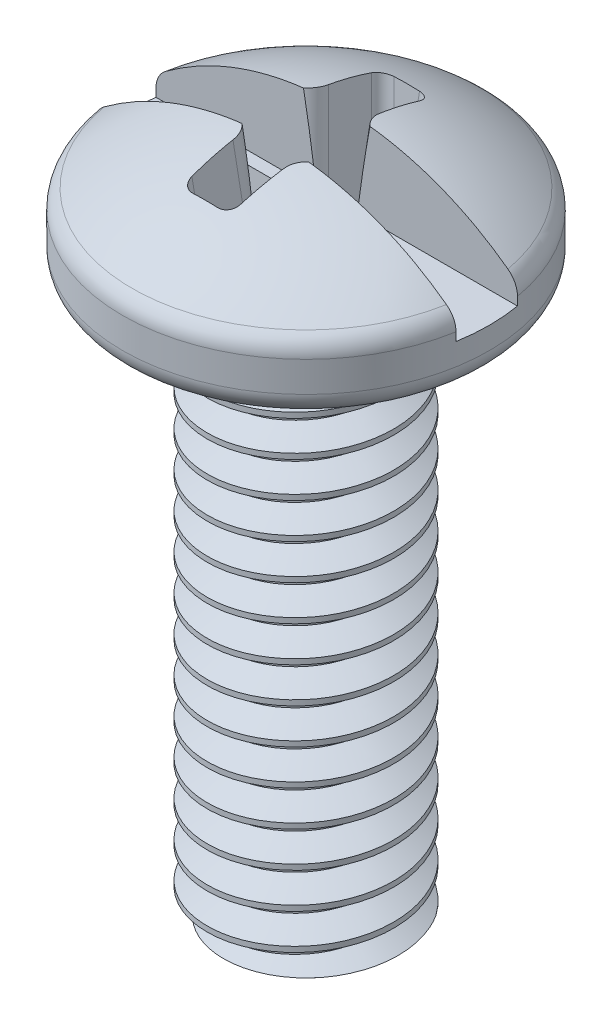
SolidWorks part; units mm, degrees
note: '?' marks a value the reader was unsure of.
material "Alloy Steel"
ref_plane "Front Plane" through (0, 0, 0) normal (0, 0, 1) x (1, 0, 0)
ref_plane "Top Plane" through (0, 0, 0) normal (0, 1, 0) x (1, 0, 0)
ref_plane "Right Plane" through (0, 0, 0) normal (1, 0, 0) x (0, 0, -1)
ref_axis "Central Axis" through (0, 0.4546, 0) along (0, -1, 0)?
sketch "Body Revolve Profile" plane through (0, 0, 0) normal (0, 0, 1) x (1, 0, 0)
  line L0 (0, 0) -> (0, -20.5337) construction
  line L1 (0, 0) -> (4.0894, 0) construction
  line L2 (4.0894, -1.7171) -> (4.0894, -2.3952)
  line L3 (3.5636, -2.921) -> (2.2098, -2.921)
  line L4 (2.0828, -3.048) -> (2.0828, -15.0874)
  line L5 (1.3208, -15.621) -> (0, -15.621)
  line L6 (0, -15.621) -> (0, 0)
  line L12 (2.0828, -15.0874) -> (1.3208, -15.621)
  line L13 (0, 0.4546) -> (0, -11.0341) construction
  arc A0 (2.0828, -3.048) -> (2.2098, -2.921) centre (2.2098, -3.048) cw
  arc A1 (3.5636, -2.921) -> (4.0894, -2.3952) centre (3.5636, -2.3952) ccw
  arc A2 (0, 0) -> (3.8798, -1.297) centre (0, -6.4516) cw
  arc A3 (3.8798, -1.297) -> (4.0894, -1.7171) centre (3.5636, -1.7171) cw
  point P5 (4.0894, -2.921)
  point P7 (2.0828, -15.621)
  point P14 (2.0828, -2.921)
  dimension "D9" = 0.127
  dimension "D2" = 0.5258
  dimension "D5" = 6.4516
  dimension "D1" = 8.1788
  dimension "D3" = 12.7
  dimension "D4" = 4.1656
  dimension "D6" = 2.921
  dimension "D14" = 0.762
  dimension "D15" = 35
revolve "Body Revolve" add sketch "Body Revolve Profile" angle 360 about L0
sketch "Phillips Cut Profile" plane through (0, 0, 0) normal (0, 1, 0) x (1, 0, 0)
  line L0 (0, 2.286) -> (0, -2.286) construction
  line L1 (-2.286, 0) -> (2.286, 0) construction
  line L2 (-0.5715, 2.286) -> (0.5715, 2.286)
  line L3 (0.5715, 2.286) -> (0.5715, 0.5715)
  line L4 (0.5715, 0.5715) -> (2.286, 0.5715)
  line L5 (2.286, 0.5715) -> (2.286, -0.5715)
  line L6 (2.286, -0.5715) -> (0.5715, -0.5715)
  line L7 (0.5715, -0.5715) -> (0.5715, -2.286)
  line L8 (0.5715, -2.286) -> (-0.5715, -2.286)
  line L9 (-0.5715, -2.286) -> (-0.5715, -0.5715)
  line L10 (-0.5715, -0.5715) -> (-2.286, -0.5715)
  line L11 (-2.286, -0.5715) -> (-2.286, 0.5715)
  line L12 (-2.286, 0.5715) -> (-0.5715, 0.5715)
  line L13 (-0.5715, 0.5715) -> (-0.5715, 2.286)
  point P2 (0, 0)
  point P6 (0, 0)
  point P21 (0, 2.286)
  point P23 (0, -2.286)
  point P25 (2.286, 0)
  point P26 (-2.286, 0)
  dimension "D1" = 1.143
  dimension "D2" = 4.572
extrude "Phillips Cut" cut sketch "Phillips Cut Profile" against normal blind 2.54 draft 5
fillet "Phillips Cut Fillet 1" radius 0.508 4 edges at (0.4582, -1.295, -0.4582) (0.4582, -1.295, 0.4582) (-0.4582, -1.295, 0.4582) (-0.4582, -1.295, -0.4582)
fillet "Phillips Cut Fillet 2" radius 0.254 8 edges at (0.4417, -1.4841, 2.1562) (-0.4417, -1.4841, 2.1562) (2.1562, -1.4841, -0.4417) (2.1562, -1.4841, 0.4417) (0.4417, -1.4841, -2.1562) (-0.4417, -1.4841, -2.1562) (-2.1562, -1.4841, 0.4417) (-2.1562, -1.4841, -0.4417)
sketch "Flathead Slot Cut Profile" plane through (0, 0, 0) normal (0, 1, 0) x (1, 0, 0)
  line L1 (-4.0894, 0.6858) -> (4.0894, 0.6858)
  line L2 (-4.0894, 0.6858) -> (-4.0894, -0.6858)
  line L3 (-4.0894, -0.6858) -> (4.0894, -0.6858)
  line L4 (4.0894, 0.6858) -> (4.0894, -0.6858)
  line L5 (-4.0894, 0.6858) -> (4.0894, -0.6858) construction
  line L6 (-4.0894, -0.6858) -> (4.0894, 0.6858) construction
  circle A0 centre (0, 0) radius 4.0894 construction
  point P0 (0, 0)
  dimension "D1" = 1.3716
extrude "Flathead Slot Cut" cut sketch "Flathead Slot Cut Profile" against normal blind 1.905
sketch "Thread Sweep Cut Profile" plane through (0, 0, 0) normal (0, 0, 1) x (1, 0, 0)
  line L0 (1.499, -15.621) -> (2.2098, -15.2106) construction
  line L1 (2.2098, -15.2106) -> (2.2098, -16.0314)
  line L2 (2.2098, -16.0314) -> (1.499, -15.621) construction
  line L3 (1.499, -15.621) -> (2.2098, -15.621) construction
  line L4 (-1.3208, -15.621) -> (1.3208, -15.621) construction
  line L5 (0, 0) -> (0, -20.5337) construction
  line L6 (0, 0) -> (0, -20.5337) construction
  line L7 (2.2098, -15.2106) -> (1.585, -15.5714)
  line L8 (1.585, -15.5714) -> (1.585, -15.6706)
  line L9 (1.585, -15.6706) -> (2.2098, -16.0314)
  line L10 (2.0828, -15.0874) -> (2.0828, -3.048) construction
  dimension "D1" = 60
  dimension "D2" = 3.1699
  dimension "D3" = 0.0992
  dimension "D4" = 0.127
sketch "Thread Sprial Profile" plane through (0, -15.621, 0) normal (0, -1, 0) x (1, 0, 0)
  circle A1 centre (0, 0) radius 2.0828
  dimension "D1" = 4.1656
curve "Thread Sprial" pitch 0.7937 height 12.5016 turns 15.75
sweep "Thread Sweep Cut" cut profiles "Thread Sweep Cut Profile" path "Thread Sprial" align with end faces yes
